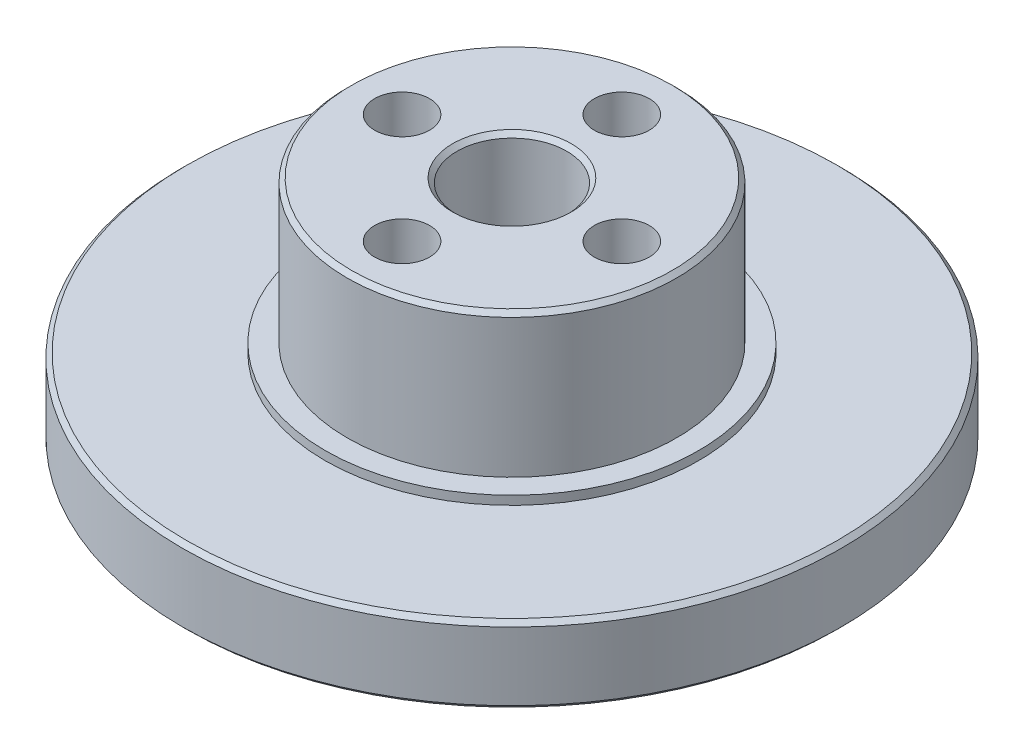
SolidWorks part; units mm, degrees
ref_plane "前视基准面" through (0, 0, 0) normal (0, 0, 1) x (1, 0, 0)
ref_plane "上视基准面" through (0, 0, 0) normal (0, 1, 0) x (1, 0, 0)
ref_plane "右视基准面" through (0, 0, 0) normal (1, 0, 0) x (0, 0, -1)
other "Configuration Table"
sketch "草图1" plane through (0, 0, 0) normal (0, 1, 0) x (1, 0, 0)
  circle A0 centre (0, 0) radius 11.525 construction
  circle A1 centre (0, 11.525) radius 2.075
  circle A2 centre (9.9809, 5.7625) radius 2.075
  circle A3 centre (9.9809, -5.7625) radius 2.075
  circle A4 centre (0, -11.525) radius 2.075
  circle A5 centre (-9.9809, -5.7625) radius 2.075
  circle A6 centre (-9.9809, 5.7625) radius 2.075
  circle A8 centre (0, 0) radius 15
  point P18 (0, 0)
  dimension "D1" = 23.05
  dimension "D2" = 4.15
  dimension "D5" = 30
  dimension "D3" = 6
extrude "凸台-拉伸1" add sketch "草图1" along normal blind 2
sketch "草图2" plane through (0, 2, 0) normal (0, 1, 0) x (1, 0, 0)
  circle A0 centre (0, 0) radius 15
extrude "凸台-拉伸2" add sketch "草图2" along normal blind 1.5
sketch "草图3" plane through (0, 3.5, 0) normal (0, 1, 0) x (1, 0, 0)
  circle A0 centre (0, 0) radius 8.5
  dimension "D1" = 17
extrude "凸台-拉伸3" add sketch "草图3" along normal blind 0.4
sketch "草图4" plane through (0, 3.9, 0) normal (0, 1, 0) x (1, 0, 0)
  circle A0 centre (0, 0) radius 7.5
  dimension "D1" = 15
extrude "凸台-拉伸4" add sketch "草图4" along normal blind 6.5
sketch "草图5" plane through (0, 10.4, 0) normal (0, 1, 0) x (1, 0, 0)
  circle A0 centre (0, 5) radius 1.25
  circle A1 centre (5, 0) radius 1.25
  circle A2 centre (0, -5) radius 1.25
  circle A3 centre (-5, 0) radius 1.25
  circle A4 centre (0, 0) radius 2.5
  point P12 (0, 0)
  dimension "D1" = 2.5
  dimension "D2" = 5
  dimension "D4" = 5
  dimension "D3" = 4
extrude "切除-拉伸1" cut sketch "草图5" against normal blind 5
chamfer "倒角1" distance 0.2 angle 45 10 edges at (-9.9809, 0, -3.6875) (-9.9809, 0, 7.8375) (0, 0, 13.6) (9.9809, 0, 7.8375) (9.9809, 0, -3.6875) (0, 0, -9.45) (0, 0, 15) (0, 10.4, 7.5) (0, 3.5, 15) (0, 10.4, 2.5)
sketch "草图7" plane through (0, 5.4, 0) normal (0, 1, 0) x (1, 0, 0)
  circle A2 centre (0, 0) radius 2.5 construction
  circle A3 centre (0, 0) radius 2.5
extrude "切除-拉伸4" cut sketch "草图7" against normal through all
sketch "草图8" plane through (0, 0, 0) normal (0, -1, 0) x (-1, 0, 0)
  circle A0 centre (0, 0) radius 6
  dimension "D1" = 6
extrude "切除-拉伸5" cut sketch "草图8" against normal blind 2
chamfer "倒角2" distance 0.5 angle 45 3 edges at (0, 0, -6) (0, 2, -2.5) (0, 2, -6)
